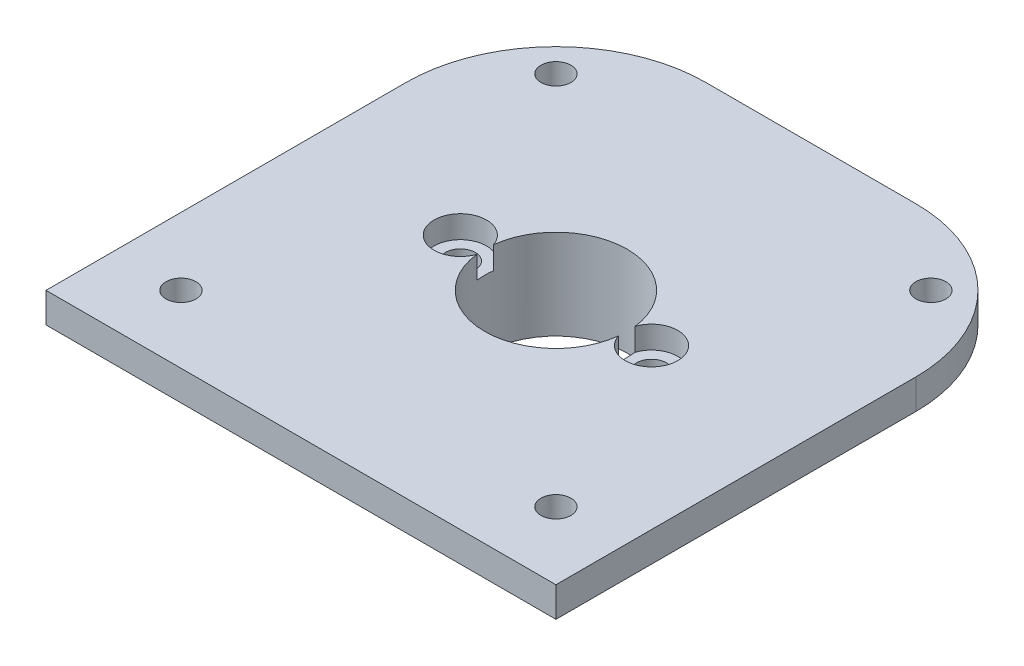
SolidWorks part; units mm, degrees
ref_plane "Front Plane" through (0, 0, 0) normal (0, 0, 1) x (1, 0, 0)
ref_plane "Top Plane" through (0, 0, 0) normal (0, 1, 0) x (1, 0, 0)
ref_plane "Right Plane" through (0, 0, 0) normal (1, 0, 0) x (0, 0, -1)
sketch "Sketch1" plane through (0, 0, 0) normal (0, 1, 0) x (1, 0, 0)
  line L0 (68, 34) -> (0, 34) construction
  line L1 (0, 0) -> (68, 0)
  line L2 (0, 0) -> (0, 68)
  line L3 (0, 68) -> (68, 68)
  line L4 (68, 0) -> (68, 68)
  line L6 (9, 9) -> (59, 9) construction
  line L7 (9, 9) -> (9, 59) construction
  line L8 (9, 59) -> (59, 59) construction
  line L9 (59, 9) -> (59, 59) construction
  line L10 (9, 9) -> (59, 59) construction
  line L11 (9, 59) -> (59, 9) construction
  circle A0 centre (59, 59) radius 2
  circle A1 centre (59, 9) radius 2
  circle A2 centre (9, 9) radius 2
  circle A3 centre (9, 59) radius 2
  circle A4 centre (21.25, 34) radius 2
  circle A5 centre (46.75, 34) radius 2
  circle A6 centre (34, 34) radius 9.5
  point P7 (34, 34)
  dimension "D3" = 4
  dimension "D4" = 12.75
  dimension "D6" = 4
  dimension "D7" = 19
  dimension "D1" = 68
  dimension "D2" = 9
  dimension "D5" = 12.75
extrude "Boss-Extrude1" add sketch "Sketch1" along normal blind 4
sketch "Sketch2" plane through (0, 0, 0) normal (0, -1, 0) x (1, 0, 0)
  circle A0 centre (34, -34) radius 19
  circle A1 centre (34, -34) radius 9.5 construction
  circle A2 centre (46.75, -34) radius 2 construction
  circle A3 centre (21.25, -34) radius 2 construction
  circle A4 centre (34, -34) radius 9.5
  circle A5 centre (46.75, -34) radius 2
  circle A6 centre (21.25, -34) radius 2
  dimension "D1" = 38
extrude "Boss-Extrude2" add sketch "Sketch2" along normal blind 8
sketch "Sketch3" plane through (0, 4, 0) normal (0, 1, 0) x (1, 0, 0)
  circle A0 centre (21.25, 34) radius 3.5
  circle A1 centre (46.75, 34) radius 3.5
  dimension "D1" = 7
extrude "Cut-Extrude1" cut sketch "Sketch3" against normal blind 3
fillet "Fillet1" radius 20 2 edges at (68, 2, -68) (0, 2, -68)
